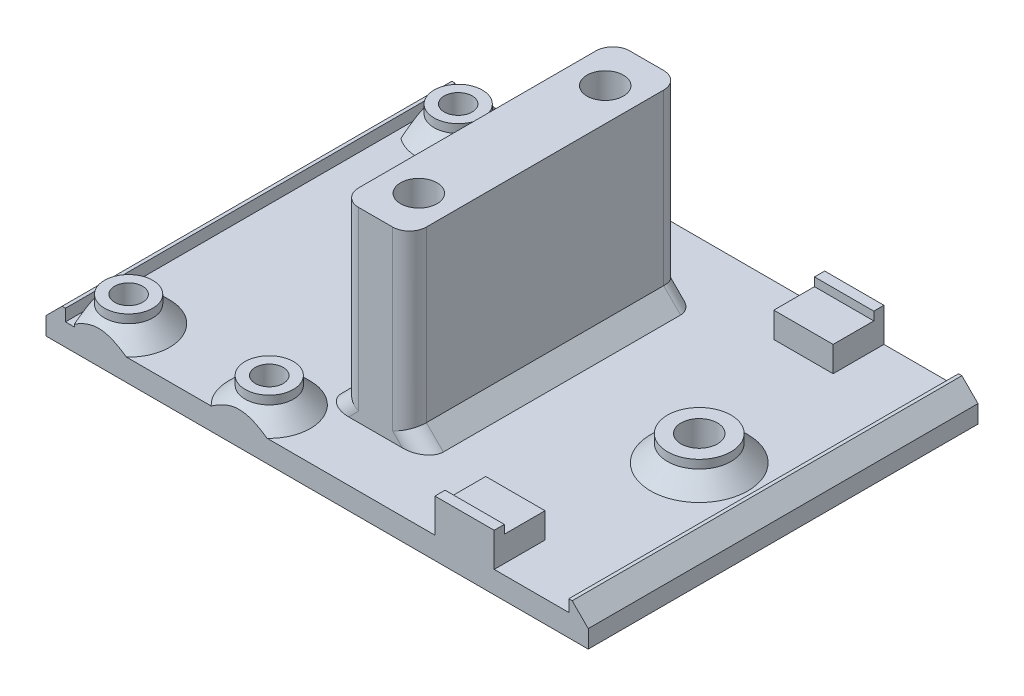
SolidWorks part; units mm, degrees
ref_plane "Płaszczyzna przednia" through (0, 0, 0) normal (0, 0, 1) x (1, 0, 0)
ref_plane "Płaszczyzna górna" through (0, 0, 0) normal (0, 1, 0) x (1, 0, 0)
ref_plane "Płaszczyzna prawa" through (0, 0, 0) normal (1, 0, 0) x (0, 0, -1)
sketch "Sketch1" plane through (0, 0, 0) normal (0, 1, 0) x (1, 0, 0)
  line L1 (0, 0) -> (64, 0)
  line L2 (0, 0) -> (0, 46)
  line L3 (0, 46) -> (64, 46)
  line L4 (64, 0) -> (64, 46)
  dimension "D1" = 46
  dimension "64" = 64
extrude "Boss-Extrude1" add sketch "Sketch1" along normal blind 2.6
hole_wizard "Ø3.3 (3.3) Diameter Hole1" positions "Sketch2" profile "Sketch3" hole size "Ø3.3" standard "DIN" end condition through all
sketch "Sketch2" plane through (0, 2.6, 0) normal (0, 1, 0) x (1, 0, 0)
  point P0 (22.8, 42.45)
  point P3 (6.2, 42.45)
  point P6 (6.2, 3.55)
  point P9 (22.8, 3.55)
sketch "Sketch3" plane through (22.8, 2.6, -42.45) normal (1, 0, 0) x (0, 0, 1)
  line L0 (0, 0) -> (0, 2.6)
  line L1 (0, 2.6) -> (1.65, 2.6)
  line L2 (1.65, 2.6) -> (1.65, 0)
  line L5 (1.65, 0) -> (0, 0)
  line L11 (0, -6.35) -> (0, 107.95) construction
  dimension "Thru Hole Dia." = 3.3
  dimension "Thru Hole Depth" = 2.6
sketch "Sketch4" plane through (0, 2.6, 0) normal (0, 1, 0) x (1, 0, 0)
  circle A0 centre (6.2, 3.55) radius 1.65 construction
  circle A1 centre (22.8, 3.55) radius 1.65 construction
  circle A2 centre (22.8, 42.45) radius 1.65 construction
  circle A3 centre (6.2, 42.45) radius 1.65 construction
  circle A4 centre (6.2, 3.55) radius 1.65
  circle A5 centre (22.8, 3.55) radius 1.65
  circle A6 centre (22.8, 42.45) radius 1.65
  circle A7 centre (6.2, 42.45) radius 1.65
  circle A8 centre (6.2, 42.45) radius 2.85
  circle A9 centre (22.8, 42.45) radius 2.85
  circle A10 centre (22.8, 3.55) radius 2.85
  circle A11 centre (6.2, 3.55) radius 2.85
  dimension "D1" = 1.2
extrude "Boss-Extrude2" add sketch "Sketch4" along normal blind 3
chamfer "Chamfer1" distance 2 angle 45 4 edges at (22.8, 2.6, -6.4) (6.2, 2.6, -6.4) (22.8, 2.6, -45.3) (6.2, 2.6, -45.3)
sketch "Sketch6" plane through (0, 2.6, 0) normal (0, 1, 0) x (1, 0, 0)
  line L1 (3.35, 46) -> (0, 46)
  line L2 (3.35, 46) -> (3.35, 0)
  line L3 (3.35, 0) -> (0, 0)
  line L4 (0, 46) -> (0, 0)
  circle A0 centre (6.2, 3.55) radius 2.85 construction
  circle A1 centre (6.2, 42.45) radius 2.85 construction
  circle A2 centre (6.2, 3.55) radius 2.85
  circle A3 centre (6.2, 42.45) radius 2.85
  arc M8 (9.5045, 46) -> (2.8955, 46) centre (6.2, 42.45) cw
  arc M12 (2.8955, 0) -> (9.5045, 0) centre (6.2, 3.55) cw
extrude "Cut-Extrude2" cut sketch "Sketch6" along normal through all contours A3 L2 L1 M8 | A2 L2 L3 M12 region at (2.5286, 2.6, -42.4201) region at (2.5286, 2.6, -3.5799)
hole_wizard "Ø4.3 (4.3) Diameter Hole1" positions "Sketch7" profile "Sketch8" hole size "Ø4.3" standard "DIN" end condition through all
sketch "Sketch7" plane through (0, 2.6, 0) normal (0, 1, 0) x (1, 0, 0)
  point P0 (54.1, 23)
sketch "Sketch8" plane through (54.1, 2.6, -23) normal (1, 0, 0) x (0, 0, 1)
  line L0 (0, 0) -> (0, 2.6)
  line L1 (0, 2.6) -> (2.15, 2.6)
  line L2 (2.15, 2.6) -> (2.15, 0)
  line L5 (2.15, 0) -> (0, 0)
  line L11 (0, -6.35) -> (0, 107.95) construction
  dimension "Thru Hole Dia." = 4.3
  dimension "Thru Hole Depth" = 2.6
sketch "Sketch9" plane through (0, 2.6, 0) normal (0, 1, 0) x (1, 0, 0)
  circle A0 centre (54.1, 23) radius 2.15 construction
  circle A1 centre (54.1, 23) radius 2.15
  circle A2 centre (54.1, 23) radius 3.75
  dimension "D1" = 1.6
extrude "Boss-Extrude3" add sketch "Sketch9" along normal up to surface (3 mm away) up to face at (22.8, 5.6, -39.6)
chamfer "Chamfer2" distance 2 angle 45 1 edges at (54.1, 2.6, -26.75)
sketch "Sketch10" plane through (0, 2.6, 0) normal (0, 1, 0) x (1, 0, 0)
  line L0 (64, 46) -> (26.1045, 46) construction
  line L1 (52.9, 46) -> (45.9, 46)
  line L2 (52.9, 46) -> (52.9, 40)
  line L3 (52.9, 40) -> (45.9, 40)
  line L4 (45.9, 46) -> (45.9, 40)
  line L5 (26.1045, 0) -> (64, 0) construction
  line L6 (45.9, 0) -> (52.9, 0)
  line L7 (45.9, 0) -> (45.9, 6)
  line L8 (45.9, 6) -> (52.9, 6)
  line L9 (52.9, 0) -> (52.9, 6)
  line L10 (58.05, 44.5) -> (52.9, 44.5) construction
  line L11 (58.05, 28.9) -> (58.05, 47.1) construction
  line L12 (58.05, 44.5) -> (40.75, 44.5) construction
  line L14 (45.9, 42.389) -> (40.75, 42.389) construction
  line L15 (40.75, 47.1) -> (40.75, 28.9) construction
  dimension "D1" = 6
  dimension "D2" = 7
extrude "Boss-Extrude4" add sketch "Sketch10" along normal up to surface (3 mm away) up to face at (54.1, 5.6, -20.85)
sketch "Sketch11" plane through (0, 5.6, 0) normal (0, 1, 0) x (1, 0, 0)
  line L1 (52.9, 46) -> (45.9, 46)
  line L2 (52.9, 46) -> (52.9, 44.8)
  line L3 (52.9, 44.8) -> (45.9, 44.8)
  line L4 (45.9, 46) -> (45.9, 44.8)
  line L6 (45.9, 46) -> (45.9, 40) construction
  line L8 (45.9, 6) -> (45.9, 0) construction
  line L9 (52.9, 0) -> (45.9, 0)
  line L10 (52.9, 0) -> (52.9, 1.2)
  line L11 (52.9, 1.2) -> (45.9, 1.2)
  line L12 (45.9, 0) -> (45.9, 1.2)
  dimension "D1" = 1.2
  dimension "D2" = 1.2
extrude "Boss-Extrude5" add sketch "Sketch11" along normal blind 1
sketch "Sketch12" plane through (0, 2.6, 0) normal (0, 1, 0) x (1, 0, 0)
  line L0 (38.8, 29.3894) -> (35.9, 29.3894) construction
  line L1 (35.9, 39) -> (27.9, 39)
  line L2 (35.9, 39) -> (35.9, 7)
  line L3 (35.9, 7) -> (27.9, 7)
  line L4 (27.9, 39) -> (27.9, 7)
  line L5 (38.8, 44.5) -> (38.8, 1.5) construction
  line L6 (30.2552, 46) -> (30.2552, 39) construction
  line L7 (27.9, 31.5368) -> (25, 31.5368) construction
  line L8 (25, 1.5) -> (25, 44.5) construction
  line L9 (45.9, 46) -> (26.1045, 46) construction
  line L11 (30.2552, 7) -> (30.2552, 0) construction
  line L12 (26.1045, 0) -> (45.9, 0) construction
  dimension "D1" = 32
  dimension "10" = 8
extrude "Boss-Extrude6" add sketch "Sketch12" along normal up to surface (22 mm away) contours L1 L4 L3 L2 up to face at (54.1, 2.6, -28.75)
chamfer "Chamfer3" distance 2 angle 45 2 edges at (35.9, 2.6, -23) (27.9, 2.6, -23)
fillet "Fillet1" radius 2 8 edges at (27.9, 14.6, -39) (35.9, 14.6, -39) (27.9, 14.6, -7) (35.9, 14.6, -7) (26.9632, 3.6632, -39) (36.9, 3.6, -39) (26.9632, 3.6632, -7) (36.9, 3.6, -7)
hole_wizard "Ø4.3 (4.3) Diameter Hole2" positions "Sketch13" profile "Sketch15" hole size "Ø4.3" standard "DIN"
sketch "Sketch13" plane through (0, 24.6, 0) normal (0, 1, 0) x (1, 0, 0)
  point P0 (32, 34)
  point P3 (32, 12)
sketch "Sketch15" plane through (32, 24.6, -34) normal (1, 0, 0) x (0, 0, 1)
  line L0 (0, 0) -> (0, 13.2919)
  line L1 (0, 13.2919) -> (2.15, 12)
  line L2 (2.15, 12) -> (2.15, 0)
  line L5 (2.15, 0) -> (0, 0)
  line L10 (0, 13.2919) -> (-2.15, 12) construction
  line L11 (0, -6.35) -> (0, 107.95) construction
  dimension "Hole Dia." = 4.3
  dimension "Hole Depth" = 12
  dimension "Drill Angle" = 118
sketch "Sketch17" plane through (0, 2.6, 0) normal (0, 1, 0) x (1, 0, 0)
  line L0 (0, 0) -> (3.35, 0) construction
  line L1 (0, 46) -> (2.3, 46)
  line L2 (0, 46) -> (0, 0)
  line L3 (0, 0) -> (2.3, 0)
  line L4 (2.3, 46) -> (2.3, 0)
  line L5 (64, 46) -> (52.9, 46) construction
  line L6 (64, 0) -> (61.7, 0)
  line L7 (64, 0) -> (64, 46)
  line L8 (64, 46) -> (61.7, 46)
  line L9 (61.7, 0) -> (61.7, 46)
  dimension "D1" = 2.3
extrude "Boss-Extrude7" add sketch "Sketch17" along normal blind 2
chamfer "Chamfer4" distance 2.5 angle 45 2 edges at (64, 4.6, -23) (0, 4.6, -23)
sketch "Sketch19" plane through (0, 0, 0) normal (0, 0, 1) x (1, 0, 0)
  line L1 (2.3, 4.4) -> (-5.2481, 4.4)
  line L2 (2.3, 4.4) -> (2.3, 4)
  line L3 (2.3, 4) -> (-5.2481, 4)
  line L4 (-5.2481, 4.4) -> (-5.2481, 4)
  line L5 (61.7, 4.4) -> (75.0626, 4.4)
  line L6 (61.7, 4.4) -> (61.7, 4)
  line L7 (61.7, 4) -> (75.0626, 4)
  line L8 (75.0626, 4.4) -> (75.0626, 4)
  dimension "D1" = 0.4
extrude "Cut-Extrude3" cut sketch "Sketch19" against normal through all
hole_wizard "Ø4.3 (4.3) Diameter Hole3" positions "Sketch20" profile "Sketch21" hole size "Ø4.3" standard "DIN"
sketch "Sketch20" plane through (0, 0, 0) normal (0, -1, 0) x (-1, 0, 0)
  line L8 (-29.9, 39) -> (-33.9, 39)
  line L9 (-27.9, 9) -> (-27.9, 37)
  line L10 (-33.9, 7) -> (-29.9, 7)
  line L11 (-35.9, 37) -> (-35.9, 9)
  line L12 (-29.9, 39) -> (-33.9, 39)
  line L13 (-27.9, 9) -> (-27.9, 37)
  line L14 (-33.9, 7) -> (-29.9, 7)
  line L15 (-35.9, 37) -> (-35.9, 9)
  line L16 (-32, 12) -> (-32, 18) construction
  line L17 (-32, 28) -> (-32, 34) construction
  arc A8 (-27.9, 37) -> (-29.9, 39) centre (-29.9, 37) ccw
  arc A9 (-29.9, 7) -> (-27.9, 9) centre (-29.9, 9) ccw
  arc A10 (-35.9, 9) -> (-33.9, 7) centre (-33.9, 9) ccw
  arc A11 (-33.9, 39) -> (-35.9, 37) centre (-33.9, 37) ccw
  arc A12 (-27.9, 37) -> (-29.9, 39) centre (-29.9, 37) ccw
  arc A13 (-29.9, 7) -> (-27.9, 9) centre (-29.9, 9) ccw
  arc A14 (-35.9, 9) -> (-33.9, 7) centre (-33.9, 9) ccw
  arc A15 (-33.9, 39) -> (-35.9, 37) centre (-33.9, 37) ccw
  circle A16 centre (-32, 12) radius 2.15 construction
  circle A17 centre (-32, 34) radius 2.15 construction
  circle A18 centre (-32, 12) radius 2.15
  circle A19 centre (-32, 34) radius 2.15
  point P0 (-32, 28)
  point P2 (-32, 18)
  dimension "D2" = 10
  dimension "D1" = 0
sketch "Sketch21" plane through (32, 0, -28) normal (1, 0, 0) x (0, 0, -1)
  line L0 (0, 0) -> (0, 13.2919)
  line L1 (0, 13.2919) -> (2.15, 12)
  line L2 (2.15, 12) -> (2.15, 0)
  line L5 (2.15, 0) -> (0, 0)
  line L10 (0, 13.2919) -> (-2.15, 12) construction
  line L11 (0, -6.35) -> (0, 107.95) construction
  dimension "Hole Dia." = 4.3
  dimension "Hole Depth" = 12
  dimension "Drill Angle" = 118
